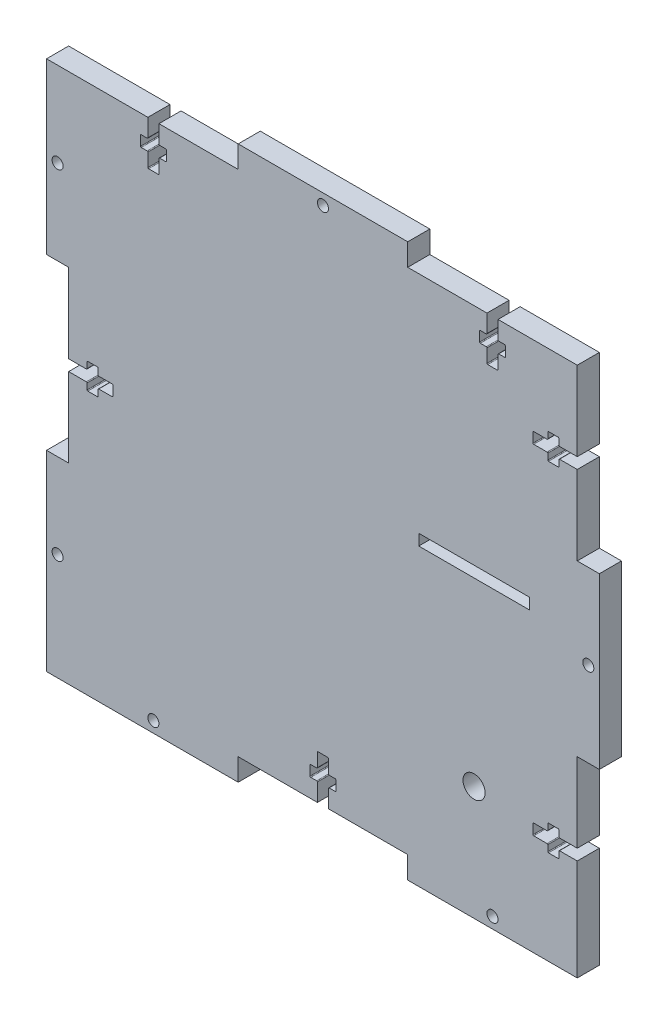
SolidWorks part; units mm, degrees
ref_plane "Front Plane" through (0, 0, 0) normal (0, 0, 1) x (1, 0, 0)
ref_plane "Top Plane" through (0, 0, 0) normal (0, 1, 0) x (1, 0, 0)
ref_plane "Right Plane" through (0, 0, 0) normal (1, 0, 0) x (0, 0, -1)
sketch "Sketch1" plane through (0, 0, 0) normal (0, 0, 1) x (1, 0, 0)
  line L0 (-69, 69) -> (-23, 69)
  line L5 (-75, -75) -> (75, -75) construction
  line L6 (-75, -75) -> (-75, 75) construction
  line L7 (-75, 75) -> (75, 75) construction
  line L8 (75, -75) -> (75, 75) construction
  line L9 (75, 23) -> (69, 23)
  line L10 (69, -23) -> (75, -23)
  line L11 (-69, -69) -> (69, -69) construction
  line L12 (-69, -69) -> (-69, 69) construction
  line L13 (-69, 69) -> (69, 69) construction
  line L14 (69, -69) -> (69, 69) construction
  line L15 (-69, -69) -> (69, 69) construction
  line L16 (69, -69) -> (69, -23)
  line L17 (-23, 69) -> (-23, 75)
  line L18 (-23, 75) -> (23, 75)
  line L19 (23, 75) -> (23, 69)
  line L20 (23, 69) -> (69, 69)
  line L21 (75, -23) -> (75, 23)
  line L22 (69, 23) -> (69, 69)
  line L23 (-75, 23) -> (-69, 23)
  line L24 (-69, 69) -> (-75, 69)
  line L25 (-75, 69) -> (-75, 23)
  line L26 (69, -69) -> (69, -75)
  line L27 (69, -75) -> (23, -75)
  line L28 (23, -75) -> (23, -69)
  line L29 (23, -69) -> (-23, -69)
  line L30 (-23, -69) -> (-23, -75)
  line L31 (-23, -75) -> (-69, -75)
  line L32 (-69, -75) -> (-69, -69) construction
  line L33 (-69, 23) -> (-69, -23)
  line L34 (-69, -23) -> (-75, -23)
  line L35 (-75, -23) -> (-75, -69)
  line L36 (-75, -69) -> (-69, -69) construction
  line L37 (-46, 69) -> (-46, -75) construction
  line L38 (-69, 69) -> (69, -69) construction
  line L39 (-75, -75) -> (-69, -75)
  line L40 (-75, -75) -> (-75, -69)
  point P0 (0, 0)
  point P6 (-7, -7)
  point P26 (0, -75)
  point P27 (-75, 0)
  dimension "D1" = 150
  dimension "D2" = 150
  dimension "D5" = 46
  dimension "D3" = 6
  dimension "D6" = 6
  dimension "D7" = 6
extrude "Box Side" add sketch "Sketch1" along normal blind 6
sketch "Sketch2" plane through (0, 0, 6) normal (0, 0, 1) x (1, 0, 0)
  line L0 (23, 72) -> (-23, 72) construction
  line L1 (23, 75) -> (23, 69) construction
  line L2 (-23, 69) -> (-23, 75) construction
  line L3 (-46, 69) -> (-46, -75) construction
  line L5 (0, 75) -> (0, 69) construction
  line L6 (-23, 75) -> (23, 75) construction
  line L7 (-69, 69) -> (69, 69) construction
  line L16 (-46, 69) -> (-46, -75) construction
  line L21 (0, -69) -> (0, 69) construction
  line L35 (-69, 69) -> (-23, 69) construction
  line L36 (-44.5, 69) -> (-44.5, 64.2)
  line L37 (-44.3, 64) -> (-42.7, 64)
  line L38 (-42.5, 63.8) -> (-42.5, 61.2)
  line L39 (-42.7, 61) -> (-44.3, 61)
  line L40 (-44.5, 60.8) -> (-44.5, 57.2)
  line L46 (-44.7, 57) -> (-47.3, 57)
  line L48 (-44.5, 69) -> (-47.5, 69)
  line L51 (-47.5, 60.8) -> (-47.5, 57.2)
  line L52 (-49.3, 61) -> (-47.7, 61)
  line L53 (-49.5, 63.8) -> (-49.5, 61.2)
  line L54 (-47.7, 64) -> (-49.3, 64)
  line L55 (-47.5, 69) -> (-47.5, 64.2)
  line L56 (47.5, 69) -> (47.5, 64.2)
  line L57 (47.7, 64) -> (49.3, 64)
  line L58 (49.5, 63.8) -> (49.5, 61.2)
  line L59 (49.3, 61) -> (47.7, 61)
  line L60 (47.5, 60.8) -> (47.5, 57.2)
  line L61 (44.5, 69) -> (47.5, 69)
  line L62 (44.7, 57) -> (47.3, 57)
  line L63 (44.5, 60.8) -> (44.5, 57.2)
  line L64 (42.7, 61) -> (44.3, 61)
  line L65 (42.5, 63.8) -> (42.5, 61.2)
  line L66 (44.3, 64) -> (42.7, 64)
  line L67 (44.5, 69) -> (44.5, 64.2)
  line L68 (-69, -69) -> (69, 69) construction
  line L69 (-69, -69) -> (69, 69) construction
  line L70 (75, 0) -> (69, 0) construction
  line L71 (72, 23) -> (72, -23) construction
  line L72 (69, 44.5) -> (64.2, 44.5)
  line L73 (64, 44.3) -> (64, 42.7)
  line L74 (63.8, 42.5) -> (61.2, 42.5)
  line L75 (61, 42.7) -> (61, 44.3)
  line L76 (60.8, 44.5) -> (57.2, 44.5)
  line L77 (57, 44.7) -> (57, 47.3)
  line L78 (69, 44.5) -> (69, 47.5)
  line L79 (60.8, 47.5) -> (57.2, 47.5)
  line L80 (61, 49.3) -> (61, 47.7)
  line L81 (63.8, 49.5) -> (61.2, 49.5)
  line L82 (64, 47.7) -> (64, 49.3)
  line L83 (69, 47.5) -> (64.2, 47.5)
  line L84 (69, -47.5) -> (64.2, -47.5)
  line L85 (64, -47.7) -> (64, -49.3)
  line L86 (63.8, -49.5) -> (61.2, -49.5)
  line L87 (61, -49.3) -> (61, -47.7)
  line L88 (60.8, -47.5) -> (57.2, -47.5)
  line L89 (69, -44.5) -> (69, -47.5)
  line L90 (57, -44.7) -> (57, -47.3)
  line L91 (60.8, -44.5) -> (57.2, -44.5)
  line L92 (61, -42.7) -> (61, -44.3)
  line L93 (63.8, -42.5) -> (61.2, -42.5)
  line L94 (64, -44.3) -> (64, -42.7)
  line L95 (69, -44.5) -> (64.2, -44.5)
  line L120 (-69, 69) -> (69, -69) construction
  line L121 (-69, 69) -> (69, -69) construction
  line L122 (-1.5, -69) -> (1.5, -69)
  line L123 (-23, -69) -> (23, -69) construction
  line L124 (1.5, -69) -> (1.5, -64.2)
  line L125 (1.7, -64) -> (3.3, -64)
  line L126 (3.5, -63.8) -> (3.5, -61.2)
  line L127 (3.3, -61) -> (1.7, -61)
  line L128 (1.5, -60.8) -> (1.5, -57.2)
  line L129 (1.3, -57) -> (-1.3, -57)
  line L130 (-1.5, -60.8) -> (-1.5, -57.2)
  line L131 (-3.3, -61) -> (-1.7, -61)
  line L132 (-3.5, -63.8) -> (-3.5, -61.2)
  line L133 (-1.7, -64) -> (-3.3, -64)
  line L134 (-1.5, -69) -> (-1.5, -64.2)
  line L135 (-69, -1.5) -> (-64.2, -1.5)
  line L136 (-64, -1.7) -> (-64, -3.3)
  line L137 (-63.8, -3.5) -> (-61.2, -3.5)
  line L138 (-61, -3.3) -> (-61, -1.7)
  line L139 (-60.8, -1.5) -> (-57.2, -1.5)
  line L140 (-57, 1.3) -> (-57, -1.3)
  line L141 (-60.8, 1.5) -> (-57.2, 1.5)
  line L142 (-61, 3.3) -> (-61, 1.7)
  line L143 (-63.8, 3.5) -> (-61.2, 3.5)
  line L144 (-64, 1.7) -> (-64, 3.3)
  line L145 (-69, 1.5) -> (-64.2, 1.5)
  line L146 (-69, -1.5) -> (-69, 1.5)
  line L147 (-69, -72) -> (-23, -72) construction
  line L148 (-23, 69) -> (-75, 69) construction
  line L149 (-23, -75) -> (-23, -69) construction
  line L150 (-69, -69) -> (-69, -75) construction
  line L151 (-75, -75) -> (-23, -75) construction
  circle A0 centre (0, 72) radius 1.5
  arc A1 (-44.5, 57.2) -> (-44.7, 57) centre (-44.7, 57.2) cw
  arc A2 (-44.3, 61) -> (-44.5, 60.8) centre (-44.3, 60.8) ccw
  arc A3 (-42.5, 61.2) -> (-42.7, 61) centre (-42.7, 61.2) cw
  arc A4 (-42.7, 64) -> (-42.5, 63.8) centre (-42.7, 63.8) cw
  arc A5 (-44.5, 64.2) -> (-44.3, 64) centre (-44.3, 64.2) ccw
  arc A6 (-47.5, 64.2) -> (-47.7, 64) centre (-47.7, 64.2) cw
  arc A7 (-49.3, 64) -> (-49.5, 63.8) centre (-49.3, 63.8) ccw
  arc A8 (-49.5, 61.2) -> (-49.3, 61) centre (-49.3, 61.2) ccw
  arc A9 (-47.7, 61) -> (-47.5, 60.8) centre (-47.7, 60.8) cw
  arc A10 (-47.5, 57.2) -> (-47.3, 57) centre (-47.3, 57.2) ccw
  arc A11 (47.5, 57.2) -> (47.3, 57) centre (47.3, 57.2) cw
  arc A12 (47.7, 61) -> (47.5, 60.8) centre (47.7, 60.8) ccw
  arc A13 (49.5, 61.2) -> (49.3, 61) centre (49.3, 61.2) cw
  arc A14 (49.3, 64) -> (49.5, 63.8) centre (49.3, 63.8) cw
  arc A15 (47.5, 64.2) -> (47.7, 64) centre (47.7, 64.2) ccw
  arc A16 (44.5, 64.2) -> (44.3, 64) centre (44.3, 64.2) cw
  arc A17 (42.7, 64) -> (42.5, 63.8) centre (42.7, 63.8) ccw
  arc A18 (42.5, 61.2) -> (42.7, 61) centre (42.7, 61.2) ccw
  arc A19 (44.3, 61) -> (44.5, 60.8) centre (44.3, 60.8) cw
  arc A20 (44.5, 57.2) -> (44.7, 57) centre (44.7, 57.2) ccw
  arc A21 (57.2, 44.5) -> (57, 44.7) centre (57.2, 44.7) cw
  arc A22 (61, 44.3) -> (60.8, 44.5) centre (60.8, 44.3) ccw
  arc A23 (61.2, 42.5) -> (61, 42.7) centre (61.2, 42.7) cw
  arc A24 (64, 42.7) -> (63.8, 42.5) centre (63.8, 42.7) cw
  arc A25 (64.2, 44.5) -> (64, 44.3) centre (64.2, 44.3) ccw
  arc A26 (64.2, 47.5) -> (64, 47.7) centre (64.2, 47.7) cw
  arc A27 (64, 49.3) -> (63.8, 49.5) centre (63.8, 49.3) ccw
  arc A28 (61.2, 49.5) -> (61, 49.3) centre (61.2, 49.3) ccw
  arc A29 (61, 47.7) -> (60.8, 47.5) centre (60.8, 47.7) cw
  arc A30 (57.2, 47.5) -> (57, 47.3) centre (57.2, 47.3) ccw
  arc A31 (57.2, -47.5) -> (57, -47.3) centre (57.2, -47.3) cw
  arc A32 (61, -47.7) -> (60.8, -47.5) centre (60.8, -47.7) ccw
  arc A33 (61.2, -49.5) -> (61, -49.3) centre (61.2, -49.3) cw
  arc A34 (64, -49.3) -> (63.8, -49.5) centre (63.8, -49.3) cw
  arc A35 (64.2, -47.5) -> (64, -47.7) centre (64.2, -47.7) ccw
  arc A36 (64.2, -44.5) -> (64, -44.3) centre (64.2, -44.3) cw
  arc A37 (64, -42.7) -> (63.8, -42.5) centre (63.8, -42.7) ccw
  arc A38 (61.2, -42.5) -> (61, -42.7) centre (61.2, -42.7) ccw
  arc A39 (61, -44.3) -> (60.8, -44.5) centre (60.8, -44.3) cw
  arc A40 (57.2, -44.5) -> (57, -44.7) centre (57.2, -44.7) ccw
  circle A41 centre (72, 0) radius 1.5
  arc A62 (1.5, -57.2) -> (1.3, -57) centre (1.3, -57.2) ccw
  arc A63 (1.7, -61) -> (1.5, -60.8) centre (1.7, -60.8) cw
  arc A64 (3.5, -61.2) -> (3.3, -61) centre (3.3, -61.2) ccw
  arc A65 (3.3, -64) -> (3.5, -63.8) centre (3.3, -63.8) ccw
  arc A66 (1.5, -64.2) -> (1.7, -64) centre (1.7, -64.2) cw
  arc A67 (-1.5, -64.2) -> (-1.7, -64) centre (-1.7, -64.2) ccw
  arc A68 (-3.3, -64) -> (-3.5, -63.8) centre (-3.3, -63.8) cw
  arc A69 (-3.5, -61.2) -> (-3.3, -61) centre (-3.3, -61.2) cw
  arc A70 (-1.7, -61) -> (-1.5, -60.8) centre (-1.7, -60.8) ccw
  arc A71 (-1.5, -57.2) -> (-1.3, -57) centre (-1.3, -57.2) cw
  arc A72 (-57.2, -1.5) -> (-57, -1.3) centre (-57.2, -1.3) ccw
  arc A73 (-61, -1.7) -> (-60.8, -1.5) centre (-60.8, -1.7) cw
  arc A74 (-61.2, -3.5) -> (-61, -3.3) centre (-61.2, -3.3) ccw
  arc A75 (-64, -3.3) -> (-63.8, -3.5) centre (-63.8, -3.3) ccw
  arc A76 (-64.2, -1.5) -> (-64, -1.7) centre (-64.2, -1.7) cw
  arc A77 (-64.2, 1.5) -> (-64, 1.7) centre (-64.2, 1.7) ccw
  arc A78 (-64, 3.3) -> (-63.8, 3.5) centre (-63.8, 3.3) cw
  arc A79 (-61.2, 3.5) -> (-61, 3.3) centre (-61.2, 3.3) cw
  arc A80 (-61, 1.7) -> (-60.8, 1.5) centre (-60.8, 1.7) ccw
  arc A81 (-57.2, 1.5) -> (-57, 1.3) centre (-57.2, 1.3) cw
  circle A82 centre (-46, -72) radius 1.5
  circle A83 centre (46, -72) radius 1.5
  circle A84 centre (-72, 46) radius 1.5
  circle A85 centre (-72, -46) radius 1.5
  point P6 (0, 72)
  point P38 (0, 0)
  point P56 (-46, 57)
  point P88 (46, 57)
  point P161 (57, 46)
  point P162 (57, -46)
  point P198 (0, -57)
  point P231 (-57, 0)
  point P234 (-42.5, 62.5)
  dimension "D1" = 3
  dimension "D2" = 0.2
  dimension "D8" = 0.2
  dimension "D14" = 3
  dimension "D4" = 3
  dimension "D7" = 1.5
  dimension "D10" = 3
  dimension "D12" = 1.5
  dimension "D9" = 12
  dimension "D11" = 5
  dimension "D13" = 7
  dimension "D3" = 12
  dimension "D5" = 7
  dimension "D6" = 5
extrude "Screw Cut-outs" cut sketch "Sketch2" against normal through all
sketch "Sketch3" plane through (0, 0, 6) normal (0, 0, 1) x (1, 0, 0)
  line L0 (23, -69) -> (50023, -69) construction
  line L4 (41, -41) -> (50041, -41) construction
  line L5 (41.5774, -47) -> (50041.5774, -47) construction
  line L8 (44, -52) -> (44, -50052) construction
  line L9 (69, -75) -> (69, -47.5) construction
  circle A0 centre (41, -44) radius 3
  circle A1 centre (41, -54) radius 15 construction
  point P15 (41, -40.1939)
  dimension "D2" = 6
  dimension "D4" = 30
  dimension "D1" = 7
  dimension "D3" = 25
extrude "Cut-Extrude1" cut sketch "Sketch3" against normal through all
sketch "Sketch4" plane through (0, 0, 0) normal (0, 0, -1) x (-1, 0, 0)
  line L0 (-72, 1.5) -> (49928, 1.5) construction
  line L1 (-56, 8) -> (-26, 8)
  line L2 (-56, 8) -> (-56, 5)
  line L3 (-56, 5) -> (-26, 5)
  line L4 (-26, 8) -> (-26, 5)
  line L5 (-75, -23) -> (-75, 23) construction
  circle A1 centre (-72, 0) radius 1.5 construction
  dimension "D1" = 3.5
  dimension "D2" = 30
  dimension "D3" = 3
  dimension "D4" = 19
extrude "Cut-Extrude2" cut sketch "Sketch4" against normal up to surface (6 mm away) up to face at (44, -44, 6)
equation "\"filletRadius\"=0.2"
equation "\"D8@Sketch2\"=\"filletRadius\""
equation "\"D2@Sketch2\"=\"filletRadius\""
equation "\"fingerWidth\"= 46"
equation "\"D5@Sketch1\"=\"fingerWidth\""
equation "\"wallThickness\"= 6"
equation "\"D3@Sketch1\" = \"wallThickness\""
equation "\"D6@Sketch1\" = \"wallThickness\""
equation "\"D7@Sketch1\" = \"wallThickness\""
equation "\"D1@Box Side\" = \"wallThickness\""
equation "\"M3\"= 3"
equation "\"D14@Sketch2\"=\"M3\""
equation "\"D1@Sketch2\"=\"M3\""
equation "\"D12@Sketch2\"=\"M3\"/2"
equation "\"nutThickness\"=3"
equation "\"D10@Sketch2\" = \"nutThickness\""
equation "\"boltLength\"= 12"
equation "\"D9@Sketch2\" = \"boltLength\""
equation "\"distanceToNut\"= 5"
equation "\"D11@Sketch2\" = \"distanceToNut\""
equation "\"D13@Sketch2\" = \"nutWidth\""
equation "\"D7@Sketch2\"=\"M3\"/2"
equation "\"D4@Sketch2\" = \"nutThickness\""
equation "\"D3@Sketch2\" = \"boltLength\""
equation "\"D5@Sketch2\" = \"nutWidth\""
equation "\"D6@Sketch2\" = \"distanceToNut\""
equation "\"sideLength\"=150"
equation "\"D1@Sketch1\"=\"sideLength\""
equation "\"D2@Sketch1\"=\"sideLength\""
equation "\"nutWidth\"=7"
